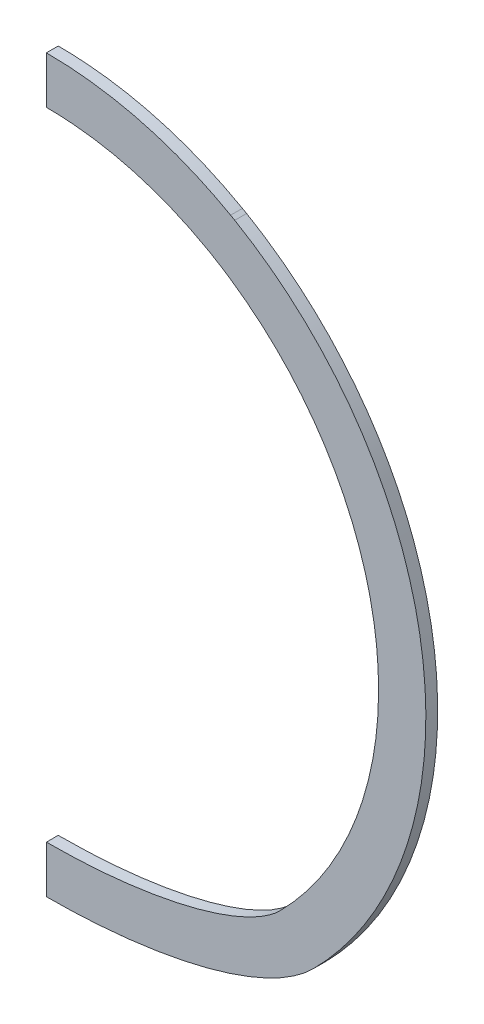
SolidWorks part; units mm, degrees
material "Balsa"
ref_plane "Front Plane" through (0, 0, 0) normal (0, 0, 1) x (1, 0, 0)
ref_plane "Top Plane" through (0, 0, 0) normal (0, 1, 0) x (1, 0, 0)
ref_plane "Right Plane" through (0, 0, 0) normal (1, 0, 0) x (0, 0, -1)
sketch "Sketch2" plane through (0, 0, 0) normal (0, 0, 1) x (1, 0, 0)
  spline S0 degree 3 poles (2568.0953, -4090.4659) (-4057.024, 3451.1389) (4945.1528, -1980.2124) (-4825.8731, 402.3844) knots -545.10296 -545.10296 -545.10296 -545.10296 547.49362 547.49362 547.49362 547.49362 only from (49.5009, 91.348) to (50.6103, 90.7129)
  spline S1 degree 3 poles (3341.4723, -3725.6669) (-100.6677, -22.1088) (-50.1916, -95.8099) (-74.4696, -70.0026) (-75.8372, -68.488) (-77.1861, -66.9319) (-78.5157, -65.3347) (-79.8244, -63.6962) (-81.5476, -61.4464) (-83.6416, -58.5297) (-85.6296, -55.5014) (-87.1622, -52.9973) (-88.2859, -51.0701) (-90.1147, -47.7724) (-92.5499, -42.8914) (-95.3516, -36.1752) (-97.8068, -28.8548) (-99.4166, -22.4927) (-100.4844, -16.9735) (-101.2174, -12.1158) (-101.8059, -6.1085) (-102.0556, 1.0556) (-101.6376, 11.9166) (-99.5817, 24.7034) (-94.9478, 39.4776) (-88.6565, 52.7081) (-80.0434, 65.5541) (-69.8712, 76.7554) (-58.637, 85.9148) (-47.202, 92.899) (-35.7905, 98.0522) (-24.0008, 101.7167) (-12.0295, 103.8942) (-3.6569, 104.3953) (0.9911, 104.3723) (2.6447, 104.3478) (5.2959, 104.2559) (8.9441, 104.0024) (12.9235, 103.5662) (16.8979, 102.9692) (20.8607, 102.2106) (24.805, 101.2899) (28.7242, 100.207) (32.6113, 98.9619) (36.4593, 97.5551) (39.9429, 96.1186) (42.4433, 94.9816) (43.9946, 94.2376) (44.9225, 93.7809) (45.8466, 93.3143) (46.7667, 92.8378) (47.6827, 92.3514) (70.4007, 80.003) (151.5153, 23.3747) (-4363.3748, 2440.7113) knots -0.313173 -0.313173 -0.313173 -0.313173 0.006795 0.013654 0.020575 0.02756 0.034609 0.041722 0.048899 0.063446 0.078252 0.085753 0.09332 0.100952 0.124124 0.148785 0.174948 0.202627 0.215494 0.232144 0.2526 0.276886 0.305032 0.363116 0.408011 0.462235 0.511576 0.564908 0.615598 0.658549 0.700916 0.742691 0.78387 0.82445 0.827809 0.831171 0.841279 0.854802 0.868378 0.882008 0.895692 0.909428 0.923217 0.93706 0.950955 0.964902 0.975398 0.978902 0.982411 0.985922 0.989437 0.992954 0.996476 1.262403 1.262403 1.262403 1.262403 only from (-71.6774, -72.9104) to (49.5009, 91.348)
  spline S2 degree 3 poles (-71.6774, -72.9104) (-72.1092, -72.4767) (-72.9729, -71.5936) (-74.4696, -70.0026) (-75.8372, -68.488) (-77.1861, -66.9319) (-78.5157, -65.3347) (-79.8244, -63.6962) (-81.5476, -61.4464) (-83.6416, -58.5297) (-85.6296, -55.5014) (-87.1622, -52.9973) (-88.2859, -51.0701) (-90.1147, -47.7724) (-92.5499, -42.8914) (-95.3516, -36.1752) (-97.8068, -28.8548) (-99.4166, -22.4927) (-100.4844, -16.9735) (-101.2174, -12.1158) (-101.8059, -6.1085) (-102.0556, 1.0556) (-101.6376, 11.9166) (-99.5817, 24.7034) (-94.9478, 39.4776) (-88.6565, 52.7081) (-80.0434, 65.5541) (-69.8712, 76.7554) (-58.637, 85.9148) (-47.202, 92.899) (-35.7905, 98.0522) (-24.0008, 101.7167) (-12.0295, 103.8942) (-3.6569, 104.3953) (0.9911, 104.3723) (2.6447, 104.3478) (5.2959, 104.2559) (8.9441, 104.0024) (12.9235, 103.5662) (16.8979, 102.9692) (20.8607, 102.2106) (24.805, 101.2899) (28.7242, 100.207) (32.6113, 98.9619) (36.4593, 97.5551) (39.9429, 96.1186) (42.4433, 94.9816) (43.9946, 94.2376) (44.9225, 93.7809) (45.8466, 93.3143) (46.7667, 92.8378) (47.6827, 92.3514) (48.5618, 91.8735) (49.1883, 91.5244) (49.5009, 91.348) knots 0 0 0 0 0.006795 0.013654 0.020575 0.02756 0.034609 0.041722 0.048899 0.063446 0.078252 0.085753 0.09332 0.100952 0.124124 0.148785 0.174948 0.202627 0.215494 0.232144 0.2526 0.276886 0.305032 0.363116 0.408011 0.462235 0.511576 0.564908 0.615598 0.658549 0.700916 0.742691 0.78387 0.82445 0.827809 0.831171 0.841279 0.854802 0.868378 0.882008 0.895692 0.909428 0.923217 0.93706 0.950955 0.964902 0.975398 0.978902 0.982411 0.985922 0.989437 0.992954 0.996476 1 1 1 1
  spline S3 degree 3 poles (49.5009, 91.348) (49.872, 91.1385) (50.2418, 90.9268) (50.6103, 90.7129) knots 0 0 0 0 1 1 1 1
  spline S4 degree 3 poles (-4193.7763, 2732.8048) (81.5381, 53.7028) (23.1515, 107.7521) (53.9325, 88.7036) (55.5798, 87.6387) (57.2181, 86.5331) (58.847, 85.3874) (60.4652, 84.2011) (62.6149, 82.559) (65.2687, 80.4032) (68.3802, 77.661) (71.4204, 74.7537) (74.3792, 71.6812) (77.2464, 68.4441) (79.5428, 65.6199) (81.3243, 63.2803) (82.6352, 61.4798) (83.9151, 59.6395) (85.6826, 56.9767) (87.8969, 53.3695) (90.4626, 48.6769) (92.8892, 43.6261) (95.1327, 38.2157) (97.1465, 32.4482) (98.8821, 26.3306) (100.2892, 19.8751) (101.2586, 13.4739) (101.8173, 7.2467) (102.0152, 1.305) (101.8786, -4.6242) (101.3926, -10.7347) (100.5371, -16.8676) (99.3294, -22.8638) (97.8936, -28.3722) (96.657, -32.2698) (95.7856, -34.7444) (95.046, -36.7643) (93.9532, -39.5358) (92.4358, -43.007) (90.8217, -46.3649) (89.1186, -49.6082) (87.3342, -52.7363) (85.4757, -55.7486) (83.5505, -58.6453) (81.5655, -61.4266) (79.3077, -64.3807) (77.437, -66.6472) (76.0073, -68.2889) (75.2951, -69.0897) (74.579, -69.8782) (73.8594, -70.6545) (73.1363, -71.4184) (59.0939, -85.9325) (120.7935, -16.6257) (-3396.6628, -3673.2191) knots -0.504739 -0.504739 -0.504739 -0.504739 0.010157 0.020393 0.030709 0.041103 0.051576 0.062128 0.072758 0.094254 0.116062 0.138181 0.16061 0.183347 0.206391 0.218027 0.22974 0.241529 0.253393 0.280162 0.30828 0.337739 0.36853 0.400644 0.434071 0.4688 0.504821 0.536145 0.567394 0.59857 0.62967 0.664059 0.696204 0.726123 0.75383 0.760691 0.767516 0.787768 0.807688 0.827278 0.84654 0.865477 0.884089 0.902378 0.920346 0.937994 0.961032 0.966703 0.97234 0.977942 0.983508 0.98904 0.994538 1.266327 1.266327 1.266327 1.266327 only from (50.6103, 90.7129) to (71.6784, -72.9104)
  spline S5 degree 3 poles (50.6103, 90.7129) (51.1284, 90.4118) (52.1672, 89.796) (53.9325, 88.7036) (55.5798, 87.6387) (57.2181, 86.5331) (58.847, 85.3874) (60.4652, 84.2011) (62.6149, 82.559) (65.2687, 80.4032) (68.3802, 77.661) (71.4204, 74.7537) (74.3792, 71.6812) (77.2464, 68.4441) (79.5428, 65.6199) (81.3243, 63.2803) (82.6352, 61.4798) (83.9151, 59.6395) (85.6826, 56.9767) (87.8969, 53.3695) (90.4626, 48.6769) (92.8892, 43.6261) (95.1327, 38.2157) (97.1465, 32.4482) (98.8821, 26.3306) (100.2892, 19.8751) (101.2586, 13.4739) (101.8173, 7.2467) (102.0152, 1.305) (101.8786, -4.6242) (101.3926, -10.7347) (100.5371, -16.8676) (99.3294, -22.8638) (97.8936, -28.3722) (96.657, -32.2698) (95.7856, -34.7444) (95.046, -36.7643) (93.9532, -39.5358) (92.4358, -43.007) (90.8217, -46.3649) (89.1186, -49.6082) (87.3342, -52.7363) (85.4757, -55.7486) (83.5505, -58.6453) (81.5655, -61.4266) (79.3077, -64.3807) (77.437, -66.6472) (76.0073, -68.2889) (75.2951, -69.0897) (74.579, -69.8782) (73.8594, -70.6545) (73.1363, -71.4184) (72.3175, -72.2647) (71.8912, -72.6967) (71.6784, -72.9104) knots 0 0 0 0 0.010157 0.020393 0.030709 0.041103 0.051576 0.062128 0.072758 0.094254 0.116062 0.138181 0.16061 0.183347 0.206391 0.218027 0.22974 0.241529 0.253393 0.280162 0.30828 0.337739 0.36853 0.400644 0.434071 0.4688 0.504821 0.536145 0.567394 0.59857 0.62967 0.664059 0.696204 0.726123 0.75383 0.760691 0.767516 0.787768 0.807688 0.827278 0.84654 0.865477 0.884089 0.902378 0.920346 0.937994 0.961032 0.966703 0.97234 0.977942 0.983508 0.98904 0.994538 1 1 1 1
  spline S6 degree 3 poles (-4835.9061, 806.008) (5645.7753, -391.3089) (-5645.7177, -391.3145) (4835.7602, 805.9912) knots -2.930767 -2.930767 -2.930767 -2.930767 3.930735 3.930735 3.930735 3.930735 weights 1 1 1 1 only from (71.6784, -72.9104) to (-71.6774, -72.9104)
  spline S7 degree 3 poles (71.6784, -72.9104) (46.3599, -98.3417) (-46.3589, -98.3417) (-71.6774, -72.9104) knots 0 0 0 0 1 1 1 1 weights 1 1 1 1
  spline S8 degree 1 poles (-62.6772, -63.9502) (43.2582, 80.2883) knots 0 0 1 1 construction
  spline S9 degree 1 poles (43.2582, 80.2883) (44.2327, 79.7303) knots 0 0 1 1 construction
  spline S10 degree 1 poles (44.2327, 79.7303) (62.6782, -63.9502) knots 0 0 1 1 construction
  spline S11 degree 1 poles (62.6782, -63.9502) (-62.6772, -63.9502) knots 0 0 1 1 construction
  spline S12 degree 3 poles (-62.6772, -63.9502) (-62.8955, -63.7309) (-63.3217, -63.2983) (-64.0021, -62.5921) (-64.7538, -61.7946) (-65.7039, -60.7646) (-66.8046, -59.5274) (-68.5568, -57.4681) (-70.6482, -54.8355) (-73.8114, -50.469) (-77.3945, -44.7561) (-82.3029, -35.1354) (-86.8108, -22.36) (-90.3543, -0.9674) (-87.6499, 26.3501) (-73.3334, 55.9721) (-49.624, 78.7088) (-24.4872, 89.3835) (-3.091, 92.1159) (13.039, 91.1975) (26.1203, 87.9966) (34.8794, 84.5248) (39.1021, 82.5104) (41.2143, 81.4108) (42.347, 80.7976) (42.9592, 80.4569) (43.2582, 80.2883) knots 0 0 0 0 0.003906 0.007812 0.011719 0.015625 0.023437 0.03125 0.046875 0.062499 0.093749 0.124999 0.187498 0.249998 0.374997 0.499996 0.624995 0.749994 0.812493 0.874993 0.937492 0.968742 0.984367 0.992179 0.996085 0.999992 0.999992 0.999992 0.999992
  spline S13 degree 3 poles (43.2582, 80.2883) (43.3397, 80.2423) (43.5025, 80.15) (43.7464, 80.0108) (43.9898, 79.871) (44.1518, 79.7773) (44.2327, 79.7303) knots 0.002022 0.002022 0.002022 0.002022 0.251014 0.500005 0.748996 0.997987 0.997987 0.997987 0.997987
  spline S14 degree 3 poles (44.2327, 79.7303) (44.5844, 79.526) (45.2596, 79.1276) (46.4154, 78.4223) (47.5738, 77.6928) (49.0079, 76.7584) (50.8048, 75.5306) (53.6072, 73.4932) (57.0034, 70.7903) (64.7641, 63.8421) (74.8536, 51.7693) (84.3118, 33.0007) (89.3026, 12.5818) (89.5941, -8.4639) (85.1673, -29.0225) (78.4712, -43.2887) (72.7378, -52.0045) (70.1455, -55.4923) (67.9548, -58.1887) (66.5372, -59.8344) (65.3768, -61.1241) (64.6361, -61.9238) (64.0489, -62.544) (63.5408, -63.0721) (63.0657, -63.5594) (62.8132, -63.8146) (62.6782, -63.9502) knots 0.000015 0.000015 0.000015 0.000015 0.007827 0.015639 0.023452 0.031264 0.046889 0.062514 0.093763 0.125013 0.250011 0.375009 0.500007 0.625005 0.750004 0.875002 0.906251 0.937501 0.953126 0.96875 0.976563 0.984375 0.988281 0.992188 0.996094 1 1 1 1
  spline S15 degree 3 poles (62.6782, -63.9502) (62.4421, -64.1873) (61.9735, -64.6322) (60.8483, -65.5949) (59.1789, -66.8259) (56.7375, -68.3252) (52.9423, -70.2888) (47.261, -72.5995) (39.2215, -74.978) (30.229, -76.8801) (17.3048, -78.7217) (0.0005, -79.6587) (-17.3038, -78.7217) (-30.228, -76.8801) (-39.2204, -74.978) (-47.2599, -72.5995) (-52.9413, -70.2888) (-56.7364, -68.3252) (-59.1779, -66.8259) (-60.8473, -65.5949) (-61.9724, -64.6322) (-62.4411, -64.1873) (-62.6772, -63.9502) knots 0 0 0 0 0.015625 0.03125 0.0625 0.09375 0.125 0.1875 0.25 0.3125 0.375 0.5 0.625 0.6875 0.75 0.8125 0.875 0.90625 0.9375 0.96875 0.984375 1 1 1 1
  dimension "D1" = 12.7
extrude "Boss-Extrude1" add sketch "Sketch2" against normal blind 3.175
sketch "Sketch3" plane through (0, 0, 0) normal (1, 0, 0) x (0, 0, -1)
  line L1 (-61.0107, 158.0584) -> (68.3789, 158.0584)
  line L2 (-61.0107, 158.0584) -> (-61.0107, -136.6623)
  line L3 (-61.0107, -136.6623) -> (68.3789, -136.6623)
  line L4 (68.3789, 158.0584) -> (68.3789, -136.6623)
extrude "Cut-Extrude1" cut sketch "Sketch3" against normal through all
